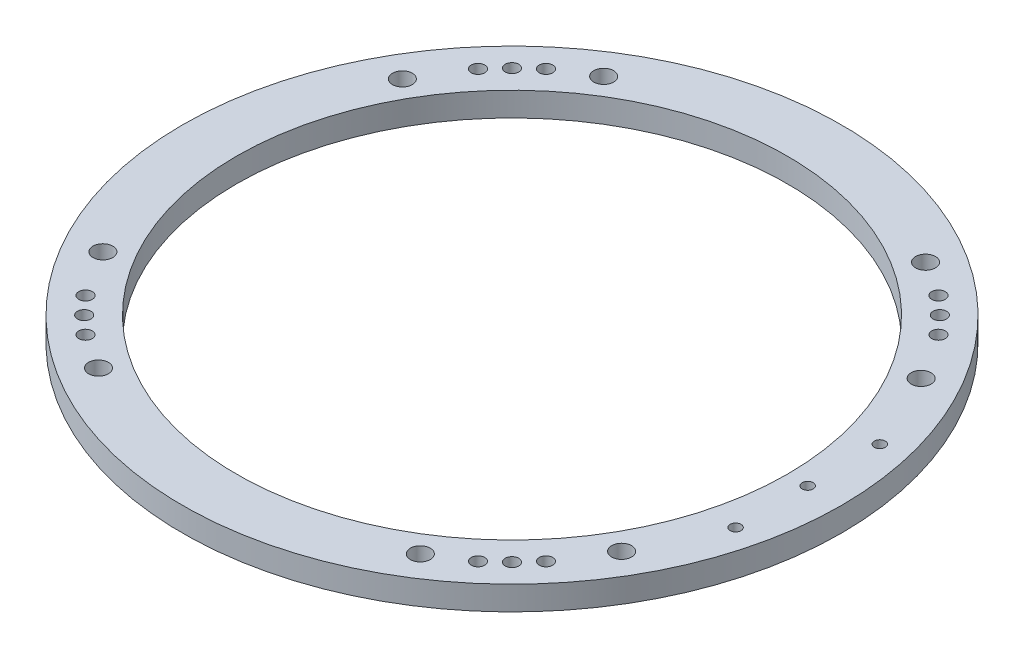
SolidWorks part; units mm, degrees
material "Oak"
ref_plane "Front Plane" through (0, 0, 0) normal (0, 0, 1) x (1, 0, 0)
ref_plane "Top Plane" through (0, 0, 0) normal (0, 1, 0) x (1, 0, 0)
ref_plane "Right Plane" through (0, 0, 0) normal (1, 0, 0) x (0, 0, -1)
sketch "Sketch1" plane through (0, 0, 0) normal (0, 0, 1) x (1, 0, 0)
  line L0 (0, 1125.8152) -> (0, -48874.1848) construction
  line L1 (145.5262, 1052.195) -> (152.4, 1052.195)
  line L9 (145.5262, 1064.895) -> (174.1012, 1064.895)
  line L10 (145.5262, 1064.895) -> (145.5262, 1052.195)
  line L11 (145.5262, 1052.195) -> (174.1012, 1052.195)
  line L12 (174.1012, 1064.895) -> (174.1012, 1052.195)
revolve "Revolve1" add sketch "Sketch1" angle 360 about L0 region at (159.8137, 1058.545, 0)
hole_wizard "9/32 (0.28125) Diameter Hole1" positions "Sketch9" profile "Sketch10" hole size "9/32" standard "ANSI Inch" end condition through all
sketch "Sketch9" plane through (0, 1052.195, 0) normal (0, -1, 0) x (-1, 0, 0)
  line L0 (0, 0) -> (113.0054, 113.0054) construction
  line L3 (0, 0) -> (103.6677, 121.6282) construction
  arc A0 (103.6677, 121.6282) -> (121.6282, 103.6677) centre (0, 0) cw
  circle A1 centre (0, 0) radius 159.8137 construction
  point P0 (103.6677, 121.6282)
  point P2 (121.6282, 103.6677)
  point P15 (113.0054, 113.0054)
sketch "Sketch10" plane through (-103.6677, 1052.195, -121.6282) normal (1, 0, 0) x (0, 0, -1)
  line L0 (0, 0) -> (0, 12.7)
  line L1 (0, 12.7) -> (3.5719, 12.7)
  line L2 (3.5719, 12.7) -> (3.5719, 0)
  line L5 (3.5719, 0) -> (0, 0)
  line L11 (0, -6.35) -> (0, 107.95) construction
  dimension "Thru Hole Dia." = 7.1437
  dimension "Thru Hole Depth" = 12.7
pattern_circular "CirPattern1" count 4 over 360 about axis through (0, 1125.8152, 0) along (0, 1, 0) of "9/32 (0.28125) Diameter Hole1"
ref_plane "Plane1" through (0, 1058.545, 0) normal (0, 1, 0) x (1, 0, 0)
hole_wizard "M5 Clearance Hole1" positions "Sketch14" profile "Sketch15" hole size "M5" standard "ANSI Metric" end condition through all
sketch "Sketch14" plane through (0, 1064.895, 0) normal (0, 1, 0) x (1, 0, 0)
  point P9 (156.21, -38.1)
  point P12 (156.21, 0)
  point P14 (156.21, 38.1)
  point P18 (0, 0)
  point P19 (156.21, 0)
  point P20 (156.21, 0)
sketch "Sketch15" plane through (156.21, 1064.895, 38.1) normal (1, 0, 0) x (0, 0, 1)
  line L0 (0, 0) -> (0, 12.7)
  line L1 (0, 12.7) -> (2.9, 12.7)
  line L2 (2.9, 12.7) -> (2.9, 0)
  line L5 (2.9, 0) -> (0, 0)
  line L11 (0, -6.35) -> (0, 107.95) construction
  dimension "Thru Hole Dia." = 5.8
  dimension "Thru Hole Depth" = 12.7
hole_wizard "Z (0.413) Diameter Hole1" positions "Sketch16" profile "Sketch17" hole size "Z" standard "ANSI Inch" end condition through all
sketch "Sketch16" plane through (0, 1064.895, 0) normal (0, 1, 0) x (1, 0, 0)
  line L0 (-137.0279, -79.1131) -> (137.0279, 79.1131) construction
  line L4 (137.0279, -79.1131) -> (-137.0279, 79.1131) construction
  line L6 (0, 0) -> (0, 158.2262) construction
  line L8 (-85.0149, -133.4467) -> (85.0149, 133.4467) construction
  line L11 (-85.0149, 133.4467) -> (85.0149, -133.4467) construction
  circle A0 centre (0, 0) radius 158.2262 construction
  circle A1 centre (0, 0) radius 145.5262 construction
  point P0 (-137.0279, -79.1131)
  point P2 (137.0279, -79.1131)
  point P4 (137.0279, 79.1131)
  point P6 (-137.0279, 79.1131)
  point P37 (-85.0149, 133.4467)
  point P39 (85.0149, 133.4467)
  point P41 (85.0149, -133.4467)
  point P43 (-85.0149, -133.4467)
  dimension "D2" = 12.7
  dimension "D1" = 120
  dimension "D3" = 65
sketch "Sketch17" plane through (-137.0279, 1064.895, 79.1131) normal (1, 0, 0) x (0, 0, 1)
  line L0 (0, 0) -> (0, 12.7)
  line L1 (0, 12.7) -> (5.2451, 12.7)
  line L2 (5.2451, 12.7) -> (5.2451, 0)
  line L5 (5.2451, 0) -> (0, 0)
  line L11 (0, -6.35) -> (0, 107.95) construction
  dimension "Thru Hole Dia." = 10.4902
  dimension "Thru Hole Depth" = 12.7
